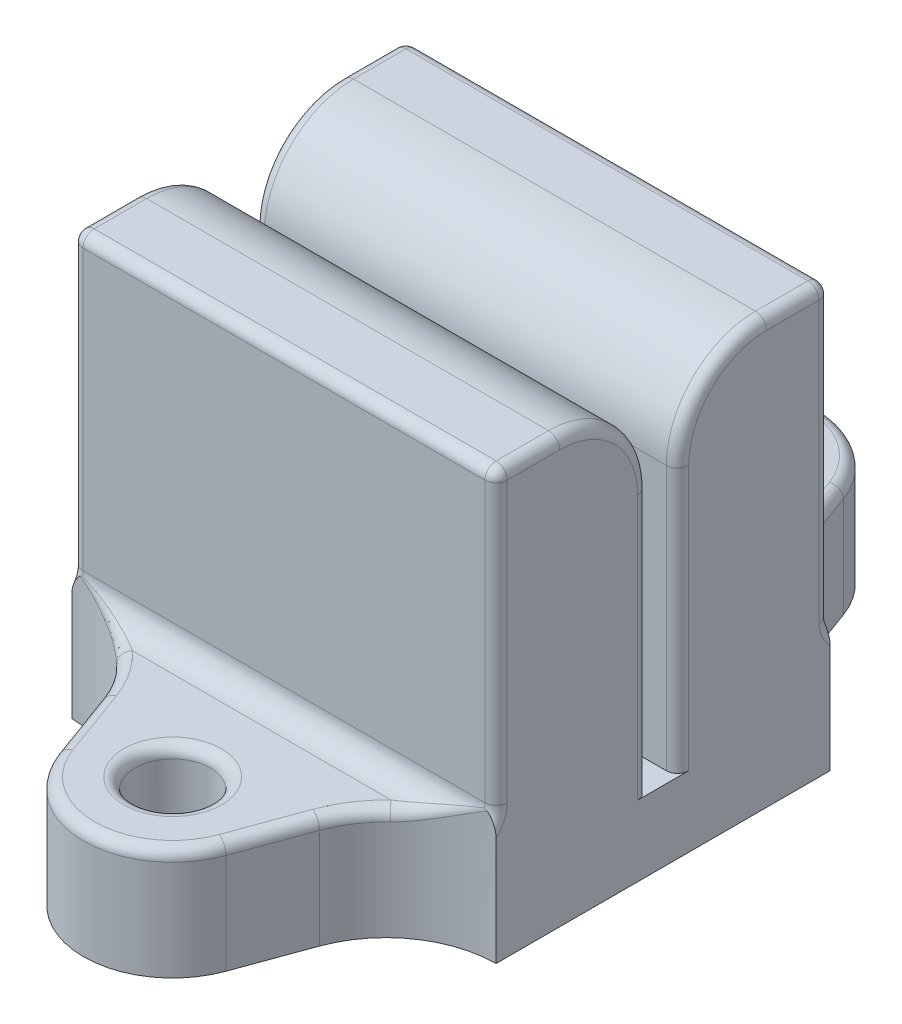
SolidWorks part; units mm, degrees
material "ABS"
ref_plane "Front Plane" through (0, 0, 0) normal (0, 0, 1) x (1, 0, 0)
ref_plane "Top Plane" through (0, 0, 0) normal (0, 1, 0) x (1, 0, 0)
ref_plane "Right Plane" through (0, 0, 0) normal (1, 0, 0) x (0, 0, -1)
sketch "Sketch1" plane through (0, 0, 0) normal (0, 1, 0) x (1, 0, 0)
  line L1 (-19.05, 15) -> (19.05, 15)
  line L2 (-19.05, 15) -> (-19.05, -15)
  line L3 (-19.05, -15) -> (19.05, -15)
  line L4 (19.05, 15) -> (19.05, -15)
  line L5 (-19.05, 15) -> (19.05, -15) construction
  line L6 (-19.05, -15) -> (19.05, 15) construction
  point P0 (0, 0)
  dimension "D1" = 38.1
  dimension "D2" = 30
extrude "Boss-Extrude1" add sketch "Sketch1" along normal blind 38.1
sketch "Sketch2" plane through (0, 0, 0) normal (1, 0, 0) x (0, 0, -1)
  line L0 (0, 20.955) -> (0, -20.955) construction
  line L1 (-1.2938, 38.1) -> (1.2938, 38.1)
  line L2 (-1.2938, 38.1) -> (-1.2938, 6.35)
  line L3 (-1.2938, 6.35) -> (1.2937, 6.35)
  line L4 (1.2938, 38.1) -> (1.2937, 6.35)
  line L5 (-15, 38.1) -> (15, 38.1) construction
  point P4 (0, 6.35)
  dimension "D1" = 2.5875
  dimension "D2" = 31.75
extrude "Cut-Extrude1" cut sketch "Sketch2" against normal through all both and the other way through all
sketch "Sketch4" plane through (0, 0, 0) normal (0, 1, 0) x (1, 0, 0)
  line L0 (-12.1531, 15) -> (-7.5175, 27.7362)
  line L1 (19.05, 15) -> (-19.05, 15) construction
  line L2 (7.5175, 27.7362) -> (12.1531, 15)
  line L3 (-12.1531, 15) -> (12.1531, 15)
  line L6 (0, -16.5) -> (0, 16.5) construction
  line L7 (-20.955, 0) -> (20.955, 0) construction
  line L8 (-12.1531, -15) -> (12.1531, -15)
  line L9 (7.5175, -27.7362) -> (12.1531, -15)
  line L10 (-12.1531, -15) -> (-7.5175, -27.7362)
  arc A0 (-7.5175, 27.7362) -> (7.5175, 27.7362) centre (0, 25) cw
  circle A1 centre (0, 25) radius 3.38
  circle A2 centre (0, -25) radius 3.38
  arc A3 (-7.5175, -27.7362) -> (7.5175, -27.7362) centre (0, -25) ccw
  point P10 (0, 15)
  point P14 (0, 33)
  dimension "D1" = 8
  dimension "D4" = 6.76
  dimension "D2" = 18
  dimension "D3" = 70
extrude "Boss-Extrude2" add sketch "Sketch4" along normal blind 10
fillet "Fillet1" radius 10 4 edges at (12.1531, 5, -15) (12.1531, 5, 15) (-12.1531, 5, 15) (-12.1531, 5, -15)
fillet "Fillet2" radius 2 2 edges at (0, 10, 15) (0, 10, -15)
fillet "Fillet3" radius 8 2 edges at (0, 38.1, -1.2938) (0, 38.1, 1.2938)
fillet "Fillet4" radius 1 34 edges at (19.05, 18.225, 1.2938) (19.05, 38.1, 12.1469) (19.05, 38.1, -12.1469) (19.05, 18.225, -1.2938) (-19.05, 18.225, -1.2938) (-19.05, 38.1, -12.1469) (-19.05, 38.1, 12.1469) (-19.05, 18.225, 1.2938) (0, 10, 21.62) (0, 10, -21.62) (19.05, 35.7569, 3.6369) (19.05, 35.7569, -3.6369) (-19.05, 35.7569, -3.6369) (-19.05, 35.7569, 3.6369) (-19.05, 25.05, 15) (-19.05, 25.05, -15) (19.05, 25.05, -15) (19.05, 25.05, 15) (0, 38.1, 15) (18.8939, 11.893, -15.0029) (11.1233, 10, -19.0425) (8.638, 10, -24.6577) (-18.8966, 11.8943, -15.0028) (-11.1233, 10, -19.0425) (-8.638, 10, -24.6577) (-18.8939, 11.893, 15.0029) (-11.1233, 10, 19.0425) (-8.638, 10, 24.6577) (18.8966, 11.8943, 15.0028) (11.1233, 10, 19.0425) (8.638, 10, 24.6577) (0, 10, -33) (0, 10, 33) (0, 38.1, -15)
equation "\"sheetMetalThickness\"= 1in / 16"
equation "\"universalHoleSize\"= 6.76mm"
equation "\"D1@Sketch1\"=1.5in"
equation "\"D1@Sketch2\"=\"sheetMetalThickness\"+1mm"
equation "\"D4@Sketch4\"=\"universalHoleSize\""
